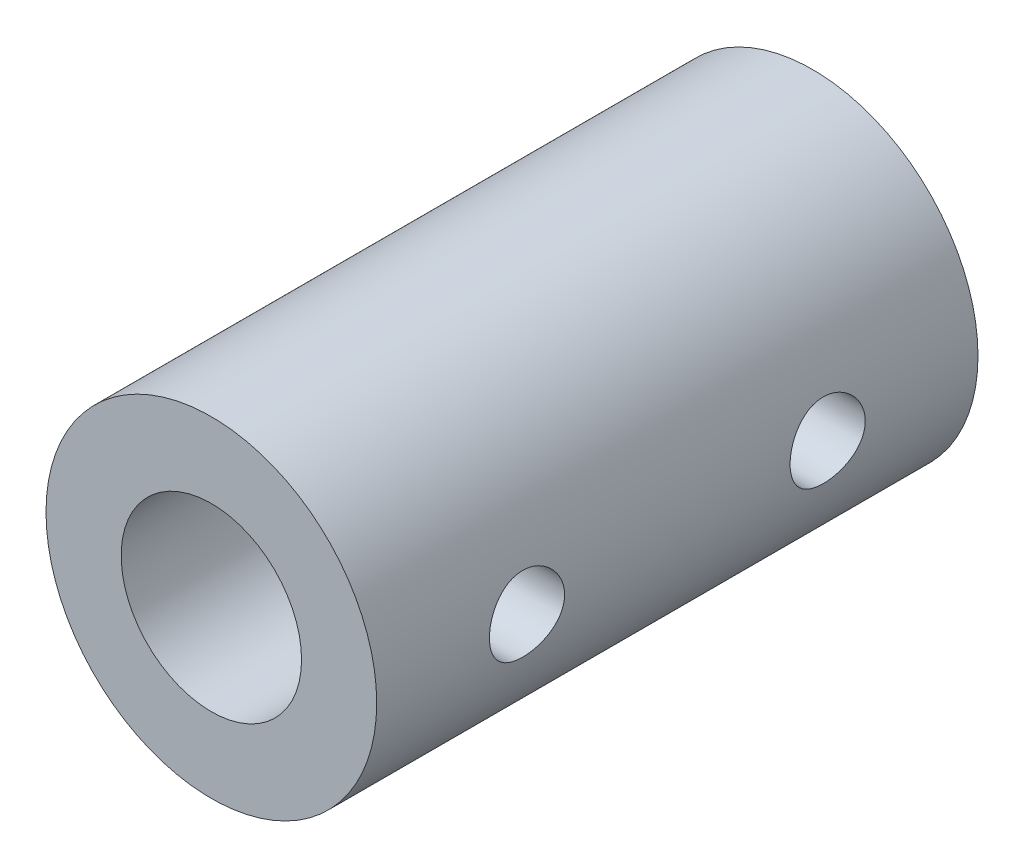
SolidWorks part; units mm, degrees
ref_plane "Alzado" through (0, 0, 0) normal (0, 0, 1) x (1, 0, 0)
ref_plane "Planta" through (0, 0, 0) normal (0, 1, 0) x (1, 0, 0)
ref_plane "Vista lateral" through (0, 0, 0) normal (1, 0, 0) x (0, 0, -1)
sketch "Croquis1" plane through (0, 0, 0) normal (0, 0, 1) x (1, 0, 0)
  circle A0 centre (0, 0) radius 3
  circle A1 centre (0, 0) radius 5.5
  dimension "D1" = 6
  dimension "D2" = 2.5
extrude "Saliente-Extruir1" add sketch "Croquis1" along normal blind 20
sketch "Croquis2" plane through (0, 0, 0) normal (1, 0, 0) x (0, 0, -1)
  line L0 (0, 5.5) -> (0, 3)
  line L1 (0, -3) -> (0, -5.5)
  line L2 (0, -3) -> (0, -5.5)
  line L3 (0, 5.5) -> (0, 3)
  line L4 (-20, 5.5) -> (-20, 3)
  line L5 (-20, -3) -> (-20, -5.5)
  line L6 (-20, -3) -> (-20, -5.5)
  line L7 (-20, 5.5) -> (-20, 3)
  line L8 (-20, 3) -> (-20, -3) construction
  line L9 (-20, 0) -> (2.5589, 0) construction
  circle A0 centre (-15, 0) radius 1.5
  circle A1 centre (-5, 0) radius 1.5
  point P8 (-15, 0)
  point P10 (-5, 0)
  dimension "D1" = 3
  dimension "D2" = 3
  dimension "D3" = 10
  dimension "D4" = 5
hole_wizard "Taladro roscado M31" positions "Croquis2" profile "Croquis4" tap size "M3" standard "DIN" end condition through all
sketch "Croquis4" plane through (0, 0, 5) normal (0, 1, 0) x (0, 0, 1)
  line L0 (0, 0) -> (0, 5.5)
  line L1 (0, 5.5) -> (1.25, 5.5)
  line L2 (1.25, 5.5) -> (1.25, 0)
  line L5 (1.25, 0) -> (0, 0)
  line L11 (0, -6.35) -> (0, 107.95) construction
  dimension "Diámetro de perforador para roscar hasta el siguiente" = 2.5
  dimension "Profundidad de perforador para roscar hasta el siguiente" = 5.5
cosmetic thread "Rosca de taladro1" parameters "D2"=3
cosmetic thread "Rosca de taladro2" parameters "D2"=3
cosmetic thread "Rosca cosmética1" parameters "D2"=3
cosmetic thread "Rosca cosmética2" parameters "D2"=3
